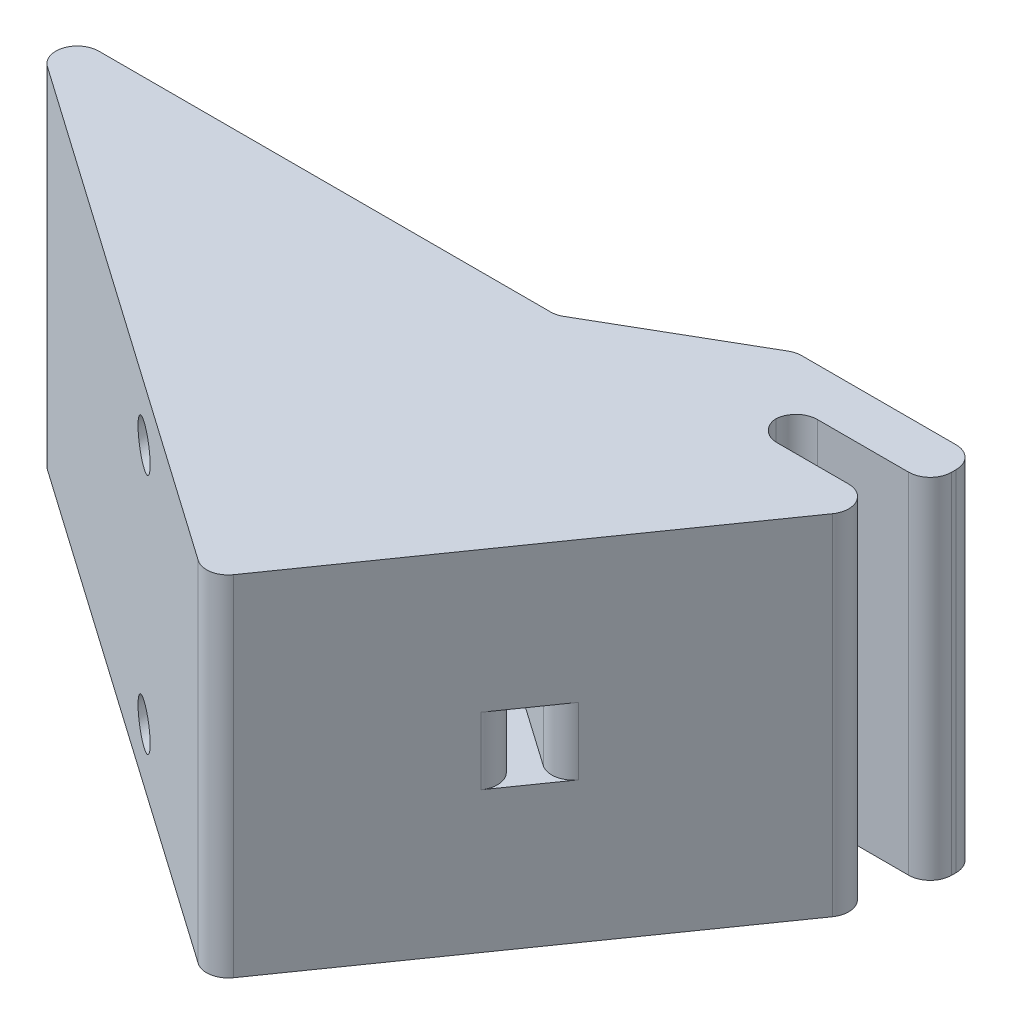
SolidWorks part; units mm, degrees
ref_plane "Front Plane" through (0, 0, 0) normal (0, 0, 1) x (1, 0, 0)
ref_plane "Top Plane" through (0, 0, 0) normal (0, 1, 0) x (1, 0, 0)
ref_plane "Right Plane" through (0, 0, 0) normal (1, 0, 0) x (0, 0, -1)
sketch "Sketch3" plane through (0, 0, 0) normal (0, 1, 0) x (1, 0, 0)
  line L0 (0, 0) -> (-101.6, 0)
  line L1 (-101.6, 0) -> (-33.4254, -47.7364)
  line L2 (-33.4254, -47.7364) -> (0, 0)
  dimension "D1" = 35
  dimension "D2" = 101.6
extrude "Boss-Extrude1" add sketch "Sketch3" along normal mid plane 41.275
sketch "Sketch1" plane through (0, 0, 0) normal (0, 1, 0) x (1, 0, 0)
  line L0 (0, 0) -> (-101.6, 0) construction
  line L1 (-21.4877, 10.3752) -> (0, 10.3752)
  line L2 (0, 10.3752) -> (0, 4.7625)
  line L3 (0, 4.7625) -> (-15.875, 4.7625)
  line L4 (-15.875, 4.7625) -> (-15.875, 0)
  line L5 (-15.875, 0) -> (-39.458, 0)
  line L6 (-39.458, 0) -> (-21.4877, 10.3752)
  line L7 (-21.4877, 10.3752) -> (-15.875, 4.7625) construction
  point P0 (-1.7294, 4.7625)
  point P3 (74.9115, 0.6788)
  point P4 (25.4512, 14.2259)
  point P5 (46.0329, 0)
  point P9 (-80.3321, 0)
  dimension "D1" = 45
  dimension "D2" = 15.875
  dimension "D3" = 7.9375
  dimension "D4" = 4.7625
  dimension "D5" = 150
extrude "Boss-Extrude2" add sketch "Sketch1" along normal mid plane 41.275
sketch "Sketch5" plane through (0, 0, 0) normal (0, 1, 0) x (1, 0, 0)
  line L0 (-56.0643, 0) -> (-18.4446, -26.3416)
  line L1 (-56.0643, 0) -> (-54.2432, 2.6008)
  line L2 (-18.4446, -26.3416) -> (-16.6235, -23.7408)
  line L3 (-54.2432, 2.6008) -> (-16.6235, -23.7408)
  line L4 (-39.458, 0) -> (-101.6, 0) construction
  line L5 (-33.4254, -47.7364) -> (0, 0) construction
  line L6 (-101.6, 0) -> (-33.4254, -47.7364) construction
  dimension "D1" = 3.175
  dimension "D2" = 6.35
extrude "Cut-Extrude1" cut sketch "Sketch5" against normal mid plane 7.9375
fillet "Fillet1" radius 2.54 13 edges at (-15.875, 0, -4.7625) (-15.875, 0, 0) (-56.0643, 0, 0) (-50.5289, 0, 0) (-18.4446, 0, 26.3416) (-16.6235, 0, 23.7408) (-39.458, 0, 0) (0, 0, 0) (0, 0, -4.7625) (0, 0, -10.3752) (-21.4877, 0, -10.3752) (-33.4254, 0, 47.7364) (-101.6, 0, 0)
sketch "Sketch6" plane through (0, 0, 0) normal (0, 0, -1) x (-1, 0, 0)
  line L0 (56.8652, 0) -> (93.5441, 0) construction
  line L1 (56.8652, 3.9688) -> (56.8652, -3.9688) construction
  line L2 (93.5441, -20.6375) -> (93.5441, 20.6375) construction
  line L3 (56.8652, 0) -> (56.8652, -14.2875) construction
  point P8 (56.8652, -14.2875)
  dimension "D1" = 14.2875
ref_axis "Axis1" through (-56.8652, -14.2875, 0) along (0, 0, -1)
ref_plane "Plane2" through (-56.8652, 0, 0) normal (1, 0, 0) x (0, 0, -1)
sketch "Sketch7" plane through (-56.8652, 0, 0) normal (1, 0, 0) x (0, 0, -1)
  line L0 (0, -18.415) -> (-1.0493, -16.6687)
  line L1 (-1.0493, -16.6687) -> (-46.7389, -16.6688)
  line L2 (-46.7389, -16.6688) -> (-46.7389, -14.2875)
  line L3 (-46.7389, -14.2875) -> (0, -14.2875) construction
  line L4 (0, -14.2875) -> (0, -18.415)
  line L5 (0, 0) -> (0, -14.2875) construction
  line L6 (0, -14.2875) -> (22.2739, -14.2875) construction
  line L7 (-46.7389, 20.6375) -> (-46.7389, -20.6375) construction
  line L8 (-46.7389, -14.2875) -> (0, -14.2875)
  point P4 (17.6484, -26.3835)
  dimension "D1" = 59
  dimension "D2" = 4.1275
  dimension "D3" = 2.3813
revolve "Cut-Revolve1" cut sketch "Sketch7" angle 360 about L3
mirror "Mirror1" about plane through (0, 0, 0) normal (0, 1, 0) of "Cut-Revolve1"
equation "\"THICKNES\" = 1.625"
equation "\"D1@Boss-Extrude1\"=\"THICKNES\""
equation "\"D1@Boss-Extrude2\"=\"THICKNES\""
